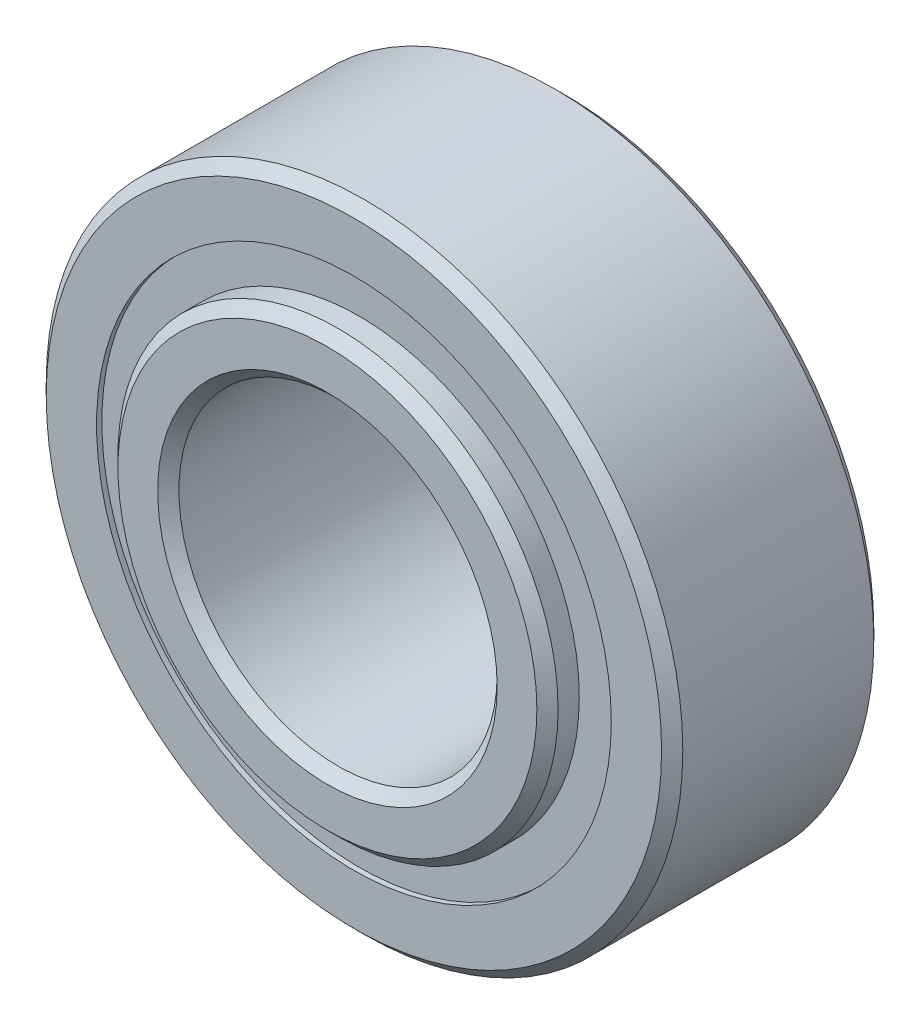
SolidWorks part; units mm, degrees
material "Cast Alloy Steel"
ref_plane "Front Plane" through (0, 0, 0) normal (0, 0, 1) x (1, 0, 0)
ref_plane "Top Plane" through (0, 0, 0) normal (0, 1, 0) x (1, 0, 0)
ref_plane "Right Plane" through (0, 0, 0) normal (1, 0, 0) x (0, 0, -1)
sketch "Sketch1" plane through (0, 0, 0) normal (1, 0, 0) x (0, 0, -1)
  line L0 (-1.5875, 0) -> (1.5875, 0) construction
  line L1 (0, 4.7625) -> (0, -4.7625) construction
  line L2 (1.4288, 4.7625) -> (-1.4288, 4.7625)
  line L3 (-1.4288, 4.7625) -> (-1.5875, 4.6037)
  line L4 (-1.5875, 4.6037) -> (-1.5875, 3.851)
  line L5 (-1.5875, 3.851) -> (-0.7056, 3.851)
  line L6 (1.5875, 3.851) -> (0.7056, 3.851)
  line L7 (1.5875, 4.6037) -> (1.5875, 3.851)
  line L8 (1.4288, 4.7625) -> (1.5875, 4.6037)
  line L9 (0, 4.7625) -> (0, 3.5719) construction
  line L10 (0, 3.5719) -> (0, 2.3813) construction
  arc A0 (-0.7056, 3.851) -> (0.7056, 3.851) centre (0, 3.5719) cw
  point P14 (0, 2.3813)
  dimension "D3" = 1.4111
  dimension "D1" = 45
  dimension "Width" = 3.175
  dimension "OD" = 9.525
  dimension "D2" = 0.1588
  dimension "Shaft Dia" = 4.7625
  dimension "D4" = 0.2791
revolve "Revolve1" add sketch "Sketch1" angle 360 about L0
sketch "Sketch3" plane through (0, 0, 0) normal (1, 0, 0) x (0, 0, -1)
  line L0 (-0.7056, 3.2928) -> (-1.9837, 3.2928) construction
  line L1 (-1.5875, 4.6037) -> (-1.5875, 3.851) construction
  line L2 (-1.4288, 4.7625) -> (-1.5875, 4.6037) construction
  line L3 (-1.9837, 3.2928) -> (-1.9837, 2.54) construction
  line L4 (-1.9837, 2.54) -> (-1.9837, 3.134)
  line L5 (-1.9837, 2.54) -> (-1.825, 2.3813)
  line L6 (-1.825, 2.3813) -> (1.825, 2.3813)
  line L8 (1.825, 2.3813) -> (1.9837, 2.54)
  line L10 (1.9837, 2.54) -> (1.9837, 3.2928) construction
  line L11 (1.9837, 3.2928) -> (0.7056, 3.2928) construction
  line L12 (0, 4.7625) -> (0, -4.7625) construction
  line L13 (1.4288, 4.7625) -> (1.5875, 4.6037) construction
  line L14 (-1.9837, 3.134) -> (-1.825, 3.2928)
  line L15 (-1.825, 3.2928) -> (-0.7056, 3.2928)
  line L16 (0.7056, 3.2928) -> (1.825, 3.2928)
  line L17 (1.825, 3.2928) -> (1.9837, 3.134)
  line L18 (1.9837, 3.134) -> (1.9837, 2.54)
  arc A1 (0.7056, 3.2928) -> (-0.7056, 3.2928) centre (0, 3.5719) cw
  arc A2 (0.7056, 3.851) -> (-0.7056, 3.851) centre (0, 3.5719) ccw construction
  dimension "D1" = 45
  dimension "Ring" = 3.9675
revolve "Revolve3" add sketch "Sketch3" angle 360 about L0
sketch "Sketch4" plane through (0, 0, 0) normal (1, 0, 0) x (0, 0, -1)
  line L0 (-0.7588, 3.5719) -> (0.7588, 3.5719)
  arc A2 (-0.7588, 3.5719) -> (0.7588, 3.5719) centre (0, 3.5719) cw
  arc A3 (0.7056, 3.851) -> (-0.7056, 3.851) centre (0, 3.5719) ccw construction
revolve "Revolve4" add sketch "Sketch4" angle 360 about L0
ref_axis "Axis1" through (0, 0, -1.5875) along (0, 0, 1)
pattern_circular "CirPattern1" count 12 every 30 about axis through (0, 0, -1.5875) along (0, 0, 1) of bodies 104
sketch "Sketch5" plane through (0, 0, 0) normal (1, 0, 0) x (0, 0, -1)
  line L0 (-1.5875, 3.851) -> (-0.7056, 3.851) construction
  line L1 (-1.5081, 3.851) -> (-0.7588, 3.851)
  line L2 (-1.5081, 3.851) -> (-1.5081, 3.2928)
  line L3 (-1.5081, 3.2928) -> (-0.7588, 3.2928)
  line L4 (-0.7588, 3.851) -> (-0.7588, 3.2928)
  line L5 (-0.7056, 3.2928) -> (-1.9837, 3.2928) construction
  line L6 (1.5875, 3.851) -> (0.7056, 3.851) construction
  line L7 (1.5081, 3.851) -> (0.7588, 3.851)
  line L8 (1.5081, 3.851) -> (1.5081, 3.2928)
  line L9 (1.5081, 3.2928) -> (0.7588, 3.2928)
  line L10 (0.7588, 3.851) -> (0.7588, 3.2928)
  line L11 (1.9837, 3.2928) -> (0.7056, 3.2928) construction
  line L12 (-1.4288, 4.7625) -> (-1.5875, 4.6037) construction
  point P18 (-1.5081, 4.6831)
revolve "Revolve5" add sketch "Sketch5" angle 360 about L0
equation "\"D2@Sketch1\" = \"Width@Sketch1\"*.05"
equation "\"D3@Sketch1\" = \"Width@Sketch1\"/2.25"
equation "\"D4@Sketch1\" = (((\"OD@Sketch1\"-\"Width@Sketch1\")/2)/3.25)/3.5"
equation "\"D2@CirPattern1\" = 360/\"Balls@CirPattern1\""
